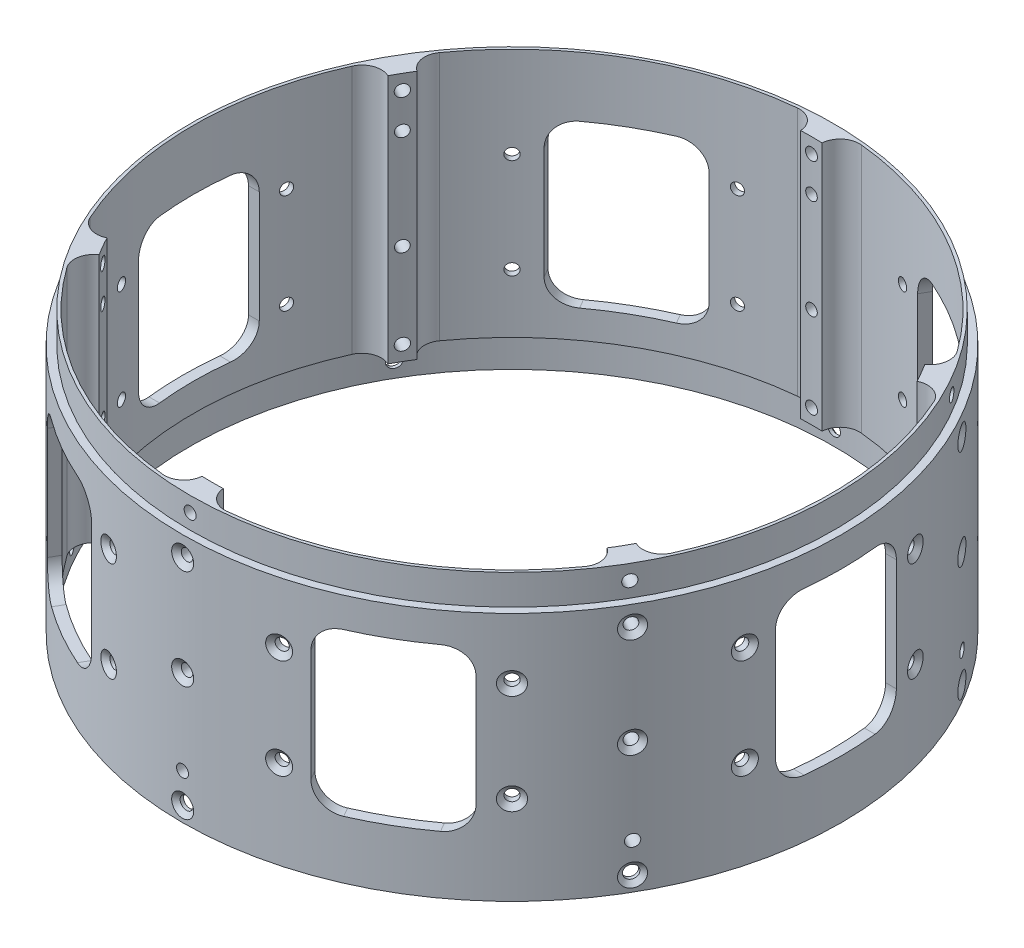
SolidWorks part; units mm, degrees
material "6061-T6 (SS)"
ref_plane "Front Plane" through (0, 0, 0) normal (0, 0, 1) x (1, 0, 0)
ref_plane "Top Plane" through (0, 0, 0) normal (0, 1, 0) x (1, 0, 0)
ref_plane "Right Plane" through (0, 0, 0) normal (1, 0, 0) x (0, 0, -1)
sketch "Sketch1" plane through (0, 0, 0) normal (0, 0, 1) x (1, 0, 0)
  line L0 (0, 42.3951) -> (0, -32.8937) construction
  line L1 (0, -35.6235) -> (0, 35.6235) construction
  line L2 (76.2, -63.5) -> (76.2, 0)
  line L3 (76.2, 0) -> (81.8896, 0)
  line L4 (81.8896, 0) -> (81.8896, -7.6708)
  line L5 (81.8896, -7.6708) -> (83.82, -7.6708)
  line L6 (83.82, -7.6708) -> (83.82, -71.12)
  line L7 (83.82, -71.12) -> (81.9404, -71.12)
  line L8 (81.9404, -71.12) -> (81.9404, -63.5)
  line L9 (81.9404, -63.5) -> (76.2, -63.5)
  line L10 (81.8896, -7.62) -> (84.2911, -7.62) construction
  dimension "D5" = 5.6896
  dimension "D10" = 76.2
  dimension "D2" = 7.62
  dimension "D4" = 7.62
  dimension "D6" = 7.62
revolve "Revolve1" add sketch "Sketch1" angle 360 about L0
sketch "Sketch2" plane through (0, 0, 0) normal (0, 1, 0) x (1, 0, 0)
  line L0 (0, 0) -> (0, 112.6688) construction
  line L1 (0, -35.6235) -> (0, 35.6235) construction
  line L2 (0, 0) -> (-128.6689, 74.287) construction
  line L3 (0, 0) -> (-50.2561, 87.0461) construction
  line L4 (0, 0) -> (-7.6343, 75.8166) construction
  arc A0 (-7.6343, 75.8166) -> (-61.8419, 44.5198) centre (0, 0) ccw construction
  arc A1 (-8.128, 80.7194) -> (-65.841, 47.3988) centre (0, 0) ccw
  arc A2 (-7.1406, 70.9138) -> (-57.8428, 41.6409) centre (0, 0) ccw
  arc A3 (-7.1406, 70.9138) -> (-8.128, 80.7194) centre (-7.6343, 75.8166) ccw
  arc A4 (-65.841, 47.3988) -> (-57.8428, 41.6409) centre (-61.8419, 44.5198) ccw
  circle A5 centre (0, 0) radius 81.8896 construction
  circle A7 centre (0, 0) radius 76.2 construction
  point P5 (-38.1, 65.9911)
  dimension "D2" = 0.762
  dimension "D1" = 60
  dimension "D3" = 30
  dimension "D4" = 5.75
extrude "Cut-Extrude1" cut sketch "Sketch2" against normal through all
pattern_circular "CirPattern1" count 6 over 360 about axis through (0, 42.3951, 0) along (0, 1, 0) of "Cut-Extrude1"
ref_plane "Plane1" through (0, 0, 83.82) normal (0, 0, 1) x (1, 0, 0)
hole_wizard "Tapped Hole for #4-40 Helicoil1" positions "Sketch3" profile "Sketch4" tap size "#4-40" standard "Helicoil® Inch"
sketch "Sketch3" plane through (0, 0, 83.82) normal (0, 0, 1) x (1, 0, 0)
  line L0 (81.8896, 0) -> (-81.8896, 0) construction
  line L1 (2.7181, 0) -> (-2.7181, 0) construction
  line L2 (2.7181, 0) -> (-2.7181, 0) construction
  line L3 (0, 0) -> (0, -3.81) construction
  line L5 (-2.7181, -63.5) -> (2.7181, -63.5) construction
  line L6 (-2.7181, -63.5) -> (2.7181, -63.5) construction
  line L7 (0, -63.5) -> (0, -59.69) construction
  point P0 (0, -3.81)
  point P20 (0, -59.69)
  dimension "D1" = 3.81
  dimension "D2" = 3.81
cosmetic thread "Hole Thread1" parameters "D1"=3.556, "D2"=3.7414
cosmetic thread "Hole Thread6" parameters "D1"=3.556, "D2"=3.7414
sketch "Sketch4" plane through (0, -3.81, 83.82) normal (1, 0, 0) x (0, -1, 0)
  line L0 (0, 0) -> (0, 26.3157)
  line L1 (0, 26.3157) -> (1.524, 25.4)
  line L2 (1.524, 25.4) -> (1.524, 0)
  line L5 (1.524, 0) -> (0, 0)
  line L10 (0, 26.3157) -> (-1.524, 25.4) construction
  line L11 (0, -6.35) -> (0, 107.95) construction
  dimension "Tap Drill Dia." = 3.048
  dimension "Tap Drill Depth" = 25.4
  dimension "Drill Angle" = 118
hole_wizard "CSK for #4 Flat Head Machine Screw (100)1" positions "Sketch5" profile "Sketch6" countersink size "#4" standard "ANSI Inch"
sketch "Sketch5" plane through (0, 0, 83.82) normal (0, 0, 1) x (1, 0, 0)
  line L0 (-2.7181, -63.5) -> (2.7181, -63.5) construction
  line L1 (-2.7181, -63.5) -> (2.7181, -63.5) construction
  line L2 (0, -63.5) -> (0, -67.31) construction
  point P0 (0, -67.31)
  dimension "D1" = 3.81
sketch "Sketch6" plane through (0, -67.31, 83.82) normal (1, 0, 0) x (0, -1, 0)
  line L0 (0, 0) -> (0, 26.3806)
  line L1 (0, 26.3806) -> (1.6319, 25.4)
  line L2 (1.6319, 25.4) -> (1.6319, 1.0284)
  line L3 (1.6319, 1.0284) -> (2.8575, 0)
  line L5 (2.8575, 0) -> (0, 0)
  line L6 (-1.6319, 1.0284) -> (-2.8575, 0) construction
  line L10 (0, 26.3806) -> (-1.632, 25.4) construction
  line L11 (0, -6.35) -> (0, 107.95) construction
  dimension "Hole Dia." = 3.2639
  dimension "Hole Depth" = 25.4
  dimension "Near C'Sink Dia." = 5.715
  dimension "Near C'Sink Angle" = 100
  dimension "Drill Angle" = 118
hole_wizard "CSK for #4 Flat Head Machine Screw (100)3" positions "Sketch12" profile "Sketch13" countersink size "#4" standard "ANSI Inch"
sketch "Sketch12" plane through (0, 0, 83.82) normal (0, 0, 1) x (1, 0, 0)
  line L0 (-2.7181, -63.5) -> (2.7181, -63.5) construction
  point P0 (0, -38.1)
  point P2 (0, -12.7)
  point P6 (0, -63.5)
  dimension "D1" = 25.4
  dimension "D2" = 50.8
sketch "Sketch13" plane through (0, -38.1, 83.82) normal (1, 0, 0) x (0, -1, 0)
  line L0 (0, 0) -> (0, 26.2852)
  line L1 (0, 26.2852) -> (1.4732, 25.4)
  line L2 (1.4732, 25.4) -> (1.4732, 1.1616)
  line L3 (1.4732, 1.1616) -> (2.8575, 0)
  line L5 (2.8575, 0) -> (0, 0)
  line L6 (-1.4732, 1.1616) -> (-2.8575, 0) construction
  line L10 (0, 26.2852) -> (-1.4732, 25.4) construction
  line L11 (0, -6.35) -> (0, 107.95) construction
  dimension "Hole Dia." = 2.9464
  dimension "Hole Depth" = 25.4
  dimension "Near C'Sink Dia." = 5.715
  dimension "Near C'Sink Angle" = 100
  dimension "Drill Angle" = 118
pattern_circular "CirPattern2" count 6 over 360 about axis through (0, 42.3951, 0) along (0, 1, 0) of "Tapped Hole for #4-40 Helicoil1", "CSK for #4 Flat Head Machine Screw (100)1", "CSK for #4 Flat Head Machine Screw (100)3"
sketch "Sketch7" plane through (0, 0, 0) normal (1, 0, 0) x (0, 0, -1)
  line L1 (-9.017, -15.24) -> (9.017, -15.24)
  line L2 (-15.367, -21.59) -> (-15.367, -50.038)
  line L3 (-9.017, -56.388) -> (9.017, -56.388)
  line L4 (15.367, -21.59) -> (15.367, -50.038)
  line L5 (-15.367, -15.24) -> (15.367, -56.388) construction
  line L6 (-15.367, -56.388) -> (15.367, -15.24) construction
  arc A0 (-15.367, -50.038) -> (-9.017, -56.388) centre (-9.017, -50.038) ccw
  arc A1 (9.017, -56.388) -> (15.367, -50.038) centre (9.017, -50.038) ccw
  arc A2 (15.367, -21.59) -> (9.017, -15.24) centre (9.017, -21.59) ccw
  arc A3 (-9.017, -15.24) -> (-15.367, -21.59) centre (-9.017, -21.59) ccw
  point P0 (0, -35.814)
  dimension "D4" = 6.35
  dimension "D1" = 41.148
  dimension "D2" = 30.734
  dimension "D3" = 15.24
extrude "Cut-Extrude2" cut sketch "Sketch7" against normal through all
sketch "Sketch9" plane through (0, -7.6708, 0) normal (0, 1, 0) x (1, 0, 0)
  line L0 (-49.5, 0) -> (-83.82, 0)
  line L1 (-50.2347, -13.4603) -> (-80.9639, -21.6942)
  line L2 (-83.82, 11.0351) -> (-83.82, -11.0351) construction
  line L3 (-83.82, -11.0351) -> (-78.1078, -32.3533) construction
  arc A0 (-83.3336, 9.017) -> (-83.3336, -9.017) centre (0, 0) ccw construction
  circle A1 centre (0, 0) radius 83.82 construction
  dimension "D1" = 15
ref_plane "Plane3" through (-80.9639, -7.6708, 21.6942) normal (-0.9659, 0, 0.2588) x (0.2588, 0, 0.9659)
hole_wizard "CSK for #4 Flat Head Machine Screw (100)2" positions "Sketch10" profile "Sketch11" countersink size "#4" standard "ANSI Inch"
sketch "Sketch10" plane through (-80.9639, -7.6708, 21.6942) normal (-0.9659, 0, 0.2588) x (0.2588, 0, 0.9659)
  line L0 (0, 0) -> (0, -15.4432) construction
  line L1 (0, -15.4432) -> (0, -40.8432) construction
  line L5 (0, -28.1432) -> (-6.4831, -28.1432) construction
  line L8 (-6.4831, -13.9192) -> (-6.4831, -42.3672) construction
  point P0 (0, -15.4432)
  point P2 (0, -40.8432)
  dimension "D1" = 25.4
sketch "Sketch11" plane through (-80.9639, -23.114, 21.6942) normal (0, 1, 0) x (0.2588, 0, 0.9659)
  line L0 (0, 0) -> (0, 26.2852)
  line L1 (0, 26.2852) -> (1.4732, 25.4)
  line L2 (1.4732, 25.4) -> (1.4732, 1.1616)
  line L3 (1.4732, 1.1616) -> (2.8575, 0)
  line L5 (2.8575, 0) -> (0, 0)
  line L6 (-1.4732, 1.1616) -> (-2.8575, 0) construction
  line L10 (0, 26.2852) -> (-1.4732, 25.4) construction
  line L11 (0, -6.35) -> (0, 107.95) construction
  dimension "Hole Dia." = 2.9464
  dimension "Hole Depth" = 25.4
  dimension "Near C'Sink Dia." = 5.715
  dimension "Near C'Sink Angle" = 100
  dimension "Drill Angle" = 118
mirror "Mirror1" about plane through (0, 0, 0) normal (0, 0, 1) of "CSK for #4 Flat Head Machine Screw (100)2"
pattern_circular "CirPattern5" count 6 over 360 about axis through (0, -7.6708, 0) along (0, 1, 0) of "Cut-Extrude2", "Mirror1"
ref_plane "Plane2" [suppressed] through (0, 0, 0) normal (-0.7071, 0, 0.7071) x (0.7071, 0, 0.7071)
sketch "Sketch8" [suppressed] plane through (0, 0, 0) normal (-0.7071, 0, 0.7071) x (0.7071, 0, 0.7071)
  line L0 (0, 0) -> (89.1919, 0) construction
  line L1 (-9.017, -17.145) -> (-6.858, -17.145)
  line L2 (-12.192, -20.32) -> (-12.192, -31.115)
  line L3 (-9.017, -34.29) -> (-6.858, -34.29)
  line L4 (-3.683, -20.32) -> (-3.683, -31.115)
  line L5 (0, 0) -> (0, -89.2767) construction
  line L6 (-83.82, -71.12) -> (83.82, -71.12) construction
  line L7 (-7.9375, -52.07) -> (-4.7625, -52.07)
  line L8 (-9.525, -53.6575) -> (-9.525, -56.8325)
  line L9 (-7.9375, -58.42) -> (-4.7625, -58.42)
  line L10 (-3.175, -53.6575) -> (-3.175, -56.8325)
  arc A0 (-9.017, -34.29) -> (-12.192, -31.115) centre (-9.017, -31.115) cw
  arc A1 (-3.683, -31.115) -> (-6.858, -34.29) centre (-6.858, -31.115) cw
  arc A2 (-3.683, -20.32) -> (-6.858, -17.145) centre (-6.858, -20.32) ccw
  arc A3 (-9.017, -17.145) -> (-12.192, -20.32) centre (-9.017, -20.32) ccw
  arc A4 (-9.525, -56.8325) -> (-7.9375, -58.42) centre (-7.9375, -56.8325) ccw
  arc A5 (-3.175, -56.8325) -> (-4.7625, -58.42) centre (-4.7625, -56.8325) cw
  arc A6 (-3.175, -53.6575) -> (-4.7625, -52.07) centre (-4.7625, -53.6575) ccw
  arc A7 (-7.9375, -52.07) -> (-9.525, -53.6575) centre (-7.9375, -53.6575) ccw
  circle A8 centre (-6.35, -48.895) radius 1.5875
  circle A9 centre (-6.35, -61.595) radius 1.5875
  point P20 (-3.175, -55.245)
  point P29 (-6.35, -58.42)
  dimension "D1" = 3.175
  dimension "D8" = 1.5875
  dimension "D11" = 3.175
  dimension "D12" = 3.175
  dimension "D2" = 8.509
  dimension "D3" = 17.145
  dimension "D4" = 17.145
  dimension "D5" = 3.683
  dimension "D6" = 6.35
  dimension "D7" = 6.35
  dimension "D9" = 6.35
  dimension "D10" = 12.7
  dimension "D13" = 3.175
  dimension "D14" = 3.175
extrude "Cut-Extrude3" [suppressed] cut sketch "Sketch8" along normal through all
equation "\"nominalLength\"=2.5"
equation "\"D8@Sketch1\"=\"nominalLength\""
equation "\"D12@Sketch8\"=\"D11@Sketch8\""
